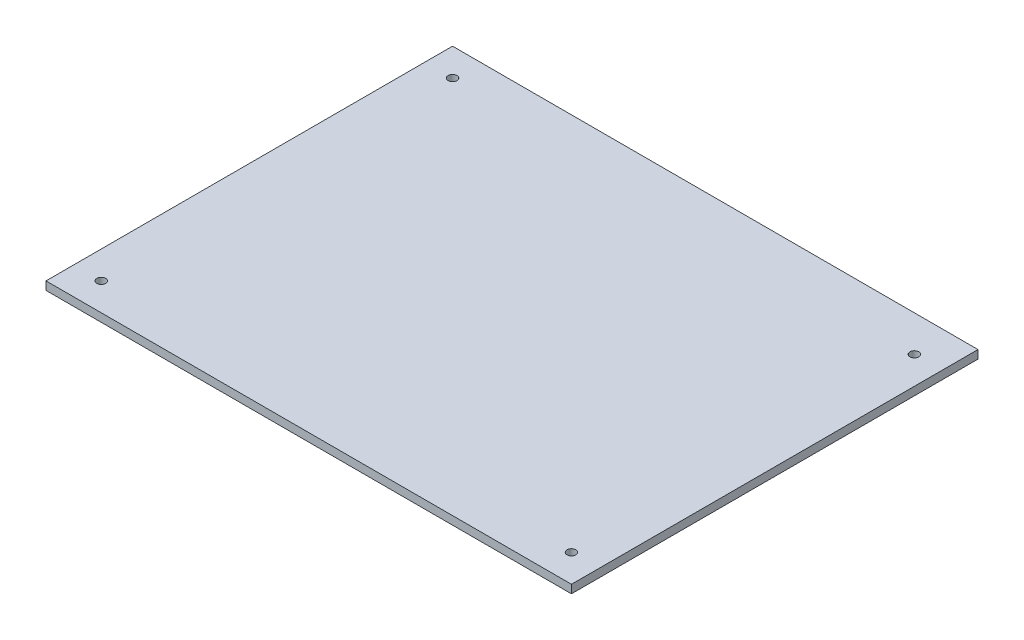
SolidWorks part; units mm, degrees
ref_plane "Front Plane" through (0, 0, 0) normal (0, 0, 1) x (1, 0, 0)
ref_plane "Top Plane" through (0, 0, 0) normal (0, 1, 0) x (1, 0, 0)
ref_plane "Right Plane" through (0, 0, 0) normal (1, 0, 0) x (0, 0, -1)
sketch "Sketch1" plane through (0, 0, 0) normal (0, 1, 0) x (1, 0, 0)
  line L1 (0, 0) -> (190, 0)
  line L2 (0, 0) -> (0, 147)
  line L3 (0, 147) -> (190, 147)
  line L4 (190, 0) -> (190, 147)
  circle A0 centre (10, 10) radius 1.6
  circle A1 centre (180, 10) radius 1.6
  circle A2 centre (10, 137) radius 1.6
  circle A3 centre (180, 134) radius 1.6
  dimension "D3" = 10
  dimension "D1" = 190
  dimension "D2" = 147
  dimension "D4" = 10
  dimension "D5" = 10
  dimension "D6" = 10
  dimension "D7" = 10
  dimension "D8" = 10
sheet metal parameters "Sheet-Metal1" thickness 3 parameters "D1"=0.7366
base flange "Base-Flange1" sketch "Sketch1" thickness 3 reverse thickness direction no parameters "D1"=0.7366
flat pattern "Flat-Pattern1" [suppressed]
sketch "Bend-Lines1" plane through (0, 0, 0) normal (0, 1, 0) x (1, 0, 0)
sketch3d "Bounding-Box1" [suppressed]
  line L0 (-190, 144, 0) -> (0, 144, 0) construction
  line L1 (-190, 0, 0) -> (0, 0, 0) construction
  line L2 (-190, 144, 0) -> (-190, 0, 0) construction
  line L3 (0, 144, 0) -> (0, 0, 0) construction
